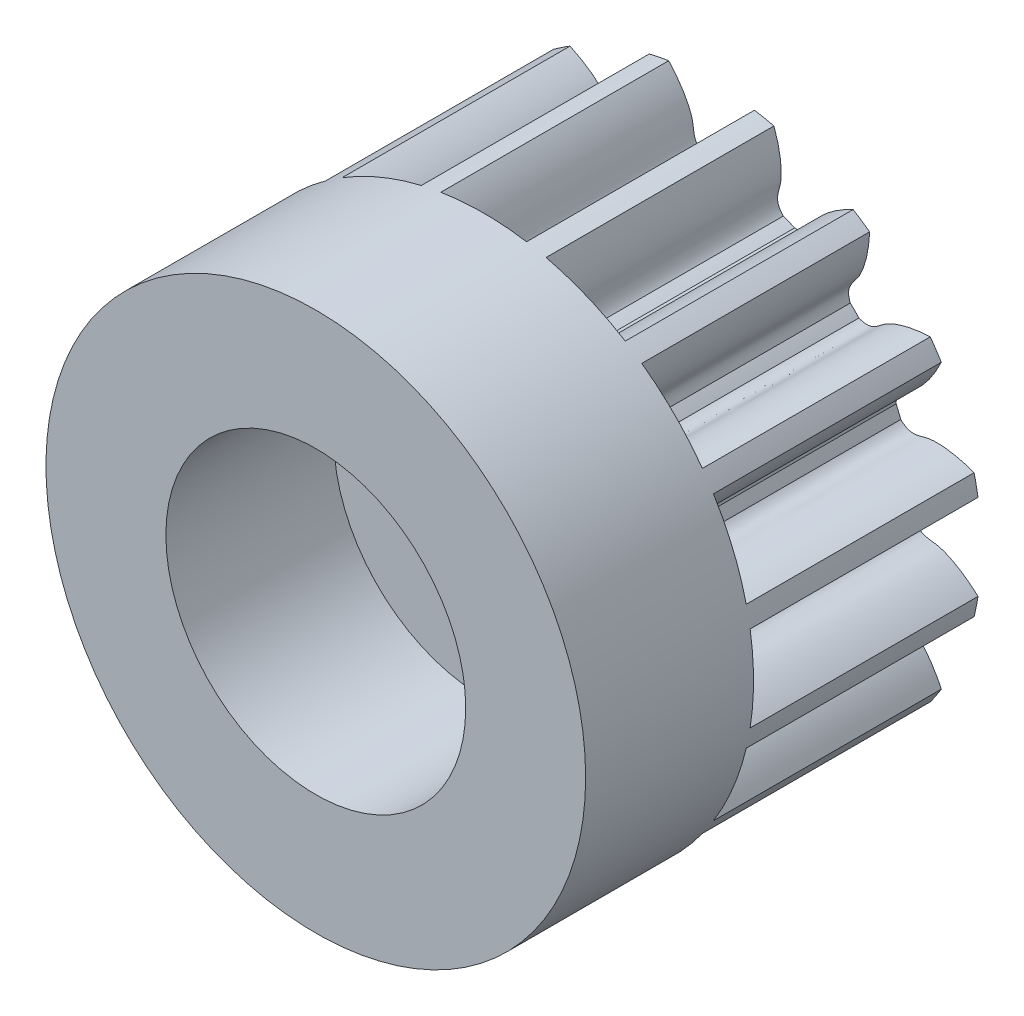
SolidWorks part; units mm, degrees
ref_plane "前视基准面" through (0, 0, 0) normal (0, 0, 1) x (1, 0, 0)
ref_plane "上视基准面" through (0, 0, 0) normal (0, 1, 0) x (1, 0, 0)
ref_plane "右视基准面" through (0, 0, 0) normal (1, 0, 0) x (0, 0, -1)
sketch "草图1" plane through (0, 0, 0) normal (0, 0, 1) x (1, 0, 0)
  circle A0 centre (0, 0) radius 4.5
extrude "凸台-拉伸1" add sketch "草图1" along normal blind 3.8
ref_axis "基准轴1" through (0, 0, 3.8) along (0, 0, -1)
sketch "草图2" plane through (0, 0, 0) normal (0, 0, 1) x (1, 0, 0)
  line L0 (0, 0) -> (0, 4.5) construction
  circle A0 centre (0, 0) radius 4.5 construction
  arc A1 (0.1017, 3.3735) -> (-0.1017, 3.3735) centre (0, 0) ccw
  arc A2 (1.5609, 5.0814) -> (-1.5609, 5.0814) centre (0, 0) ccw
  spline S0 degree 3 poles (0.1017, 3.3735) (0.3209, 3.4651) (0.2847, 3.6353) (0.3224, 3.7934) (0.3256, 3.8058) (0.3295, 3.8195) (0.334, 3.8346) (0.3394, 3.8511) (0.3455, 3.8688) (0.3526, 3.8879) (0.3605, 3.9082) (0.3695, 3.9297) (0.3794, 3.9524) (0.3905, 3.9763) (0.4027, 4.0013) (0.4161, 4.0274) (0.4307, 4.0545) (0.4466, 4.0827) (0.4638, 4.1118) (0.4823, 4.1419) (0.5023, 4.1728) (0.5238, 4.2046) (0.5467, 4.2372) (0.5712, 4.2705) (0.5973, 4.3045) (0.6249, 4.3392) (0.6543, 4.3744) (0.6853, 4.4102) (0.718, 4.4465) (0.7524, 4.4833) (0.7887, 4.5204) (0.8267, 4.5578) (0.8666, 4.5955) (0.9084, 4.6334) (0.952, 4.6715) (0.9975, 4.7096) (1.045, 4.7478) (1.0944, 4.7859) (1.1457, 4.8239) (1.1991, 4.8618) (1.2544, 4.8994) (1.3117, 4.9367) (1.3711, 4.9737) (1.4537, 5.023) (1.5175, 5.0584) (1.5609, 5.0814) knots 0 0 0 0 0.200958 0.205848 0.21139 0.217584 0.224431 0.231929 0.240079 0.248881 0.258335 0.268441 0.2792 0.29061 0.302672 0.315386 0.328753 0.342771 0.357441 0.372764 0.388738 0.405364 0.422643 0.440573 0.459155 0.47839 0.498276 0.518814 0.540005 0.561847 0.584342 0.607488 0.631287 0.655737 0.68084 0.706594 0.733001 0.760059 0.78777 0.816132 0.845147 0.874814 0.905132 0.936103 1 1 1 1
  spline S1 degree 3 poles (-0.1017, 3.3735) (-0.3209, 3.4651) (-0.2847, 3.6353) (-0.3224, 3.7934) (-0.3256, 3.8058) (-0.3295, 3.8195) (-0.334, 3.8346) (-0.3394, 3.8511) (-0.3455, 3.8688) (-0.3526, 3.8879) (-0.3605, 3.9082) (-0.3695, 3.9297) (-0.3794, 3.9524) (-0.3905, 3.9763) (-0.4027, 4.0013) (-0.4161, 4.0274) (-0.4307, 4.0545) (-0.4466, 4.0827) (-0.4638, 4.1118) (-0.4823, 4.1419) (-0.5023, 4.1728) (-0.5238, 4.2046) (-0.5467, 4.2372) (-0.5712, 4.2705) (-0.5973, 4.3045) (-0.6249, 4.3392) (-0.6543, 4.3744) (-0.6853, 4.4102) (-0.718, 4.4465) (-0.7524, 4.4833) (-0.7887, 4.5204) (-0.8267, 4.5578) (-0.8666, 4.5955) (-0.9084, 4.6334) (-0.952, 4.6715) (-0.9975, 4.7096) (-1.045, 4.7478) (-1.0944, 4.7859) (-1.1457, 4.8239) (-1.1991, 4.8618) (-1.2544, 4.8994) (-1.3117, 4.9367) (-1.3711, 4.9737) (-1.4537, 5.023) (-1.5175, 5.0584) (-1.5609, 5.0814) knots 0 0 0 0 0.200958 0.205848 0.21139 0.217584 0.224431 0.231929 0.240079 0.248881 0.258335 0.268441 0.2792 0.29061 0.302672 0.315386 0.328753 0.342771 0.357441 0.372764 0.388738 0.405364 0.422643 0.440573 0.459155 0.47839 0.498276 0.518814 0.540005 0.561847 0.584342 0.607488 0.631287 0.655737 0.68084 0.706594 0.733001 0.760059 0.78777 0.816132 0.845147 0.874814 0.905132 0.936103 1 1 1 1
extrude "切除-拉伸1" cut sketch "草图2" along normal through all
pattern_circular "阵列(圆周)1" count 16 every 22.5 about axis through (0, 0, 3.8) along (0, 0, -1) of "切除-拉伸1"
sketch "草图3" plane through (0, 0, 0) normal (0, 0, 1) x (1, 0, 0)
  circle A0 centre (0, 0) radius 4 construction
  dimension "Dn" = 8
sketch "草图4" plane through (0, 0, 3.8) normal (0, 0, 1) x (1, 0, 0)
  circle A0 centre (0, 0) radius 2.5
  circle A1 centre (0, 0) radius 4.5
  dimension "D1" = 5
  dimension "D2" = 9
extrude "凸台-拉伸2" add sketch "草图4" along normal blind 2.8
